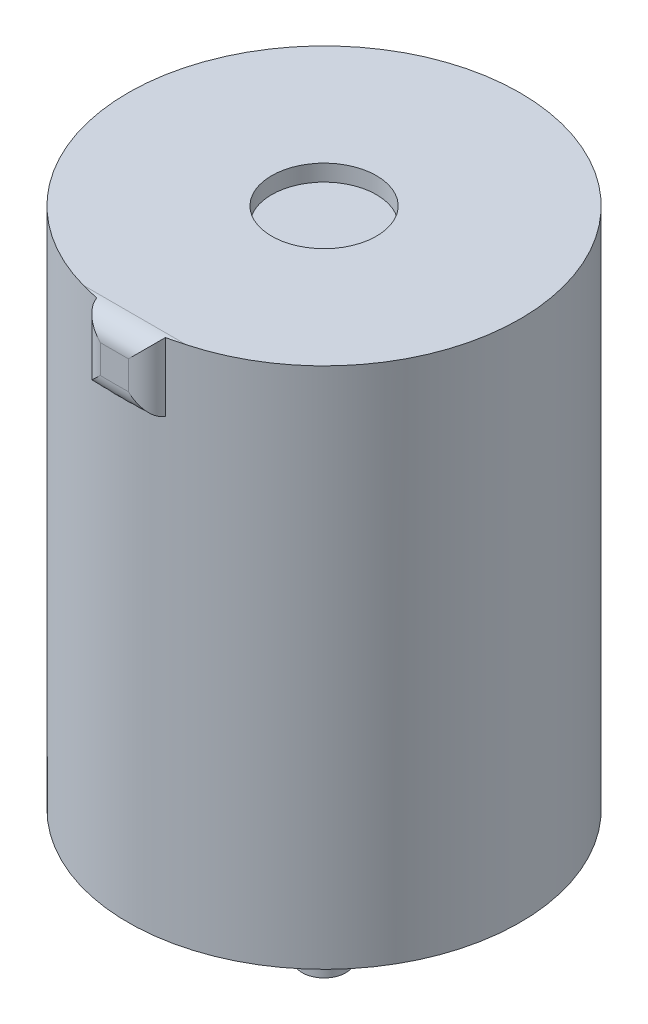
SolidWorks part; units mm, degrees
ref_plane "Front" through (0, 0, 0) normal (0, 0, 1) x (1, 0, 0)
ref_plane "Top" through (0, 0, 0) normal (0, 1, 0) x (1, 0, 0)
ref_plane "Right" through (0, 0, 0) normal (1, 0, 0) x (0, 0, -1)
sketch "Sketch1" plane through (0, 0, 0) normal (0, 0, 1) x (1, 0, 0)
  line L0 (0, -19.05) -> (3.175, -19.05)
  line L1 (3.175, -19.05) -> (3.175, 2.4)
  line L2 (3.175, 2.4) -> (7.645, 2.4)
  line L3 (7.645, 2.4) -> (7.645, 0)
  line L4 (7.645, 0) -> (28.575, 0)
  line L5 (28.575, 0) -> (28.575, 76.2)
  line L6 (28.575, 76.2) -> (7.645, 76.2)
  line L7 (7.645, 76.2) -> (7.645, 73.8)
  line L8 (7.645, 73.8) -> (0, 73.8)
  line L9 (0, 73.8) -> (0, -19.05)
  line L10 (0, 0) -> (0, 63.4299) construction
  dimension "D1" = 6.35
  dimension "D2" = 57.15
  dimension "D3" = 19.05
  dimension "D4" = 76.2
  dimension "D5" = 2.4
  dimension "D6" = 15.29
revolve "Revolve1" add sketch "Sketch1" angle 360 about L10
hole_wizard "#6-32 Tapped Hole1" positions "Sketch2" profile "Sketch4" tap size "#6-32" standard "ANSI Inch"
sketch "Sketch2" plane through (0, 0, 0) normal (0, -1, 0) x (-1, 0, 0)
  line L0 (0, 0) -> (0, 19.05) construction
  line L3 (0, 0) -> (4.9305, 18.4009) construction
  circle A0 centre (0, 0) radius 19.05
  point P0 (4.9305, 18.4009)
  dimension "D1" = 38.1
  dimension "D2" = 15
sketch "Sketch4" plane through (-4.9305, 0, -18.4009) normal (1, 0, 0) x (0, 0, -1)
  line L0 (0, 0) -> (0, 8.4327)
  line L1 (0, 8.4327) -> (1.3525, 7.62)
  line L2 (1.3525, 7.62) -> (1.3525, 0)
  line L5 (1.3525, 0) -> (0, 0)
  line L10 (0, 8.4327) -> (-1.3526, 7.62) construction
  line L11 (0, -6.35) -> (0, 107.95) construction
  dimension "Tap Drill Dia." = 2.7051
  dimension "Tap Drill Depth" = 7.62
  dimension "Drill Angle" = 118
cosmetic thread "Hole Thread1" parameters "D1"=7.01, "D2"=3.5052
pattern_circular "CirPattern1" count 4 over 360 about axis through (0, 0, 0) along (0, 1, 0) of "#6-32 Tapped Hole1"
ref_plane "Plane1" through (0, 0, 28.575) normal (0, 0, 1) x (1, 0, 0)
sketch "Sketch5" plane through (0, 0, 28.575) normal (0, 0, 1) x (1, 0, 0)
  line L0 (28.575, 76.2) -> (-28.575, 76.2) construction
  line L1 (-5, 76.2) -> (5, 76.2)
  line L2 (-5, 76.2) -> (-5, 66.2)
  line L3 (-5, 66.2) -> (5, 66.2)
  line L4 (5, 76.2) -> (5, 66.2)
  point P4 (0, 76.2)
  dimension "D1" = 10
  dimension "D2" = 10
extrude "Boss-Extrude1" add sketch "Sketch5" along normal blind 2 and the other way up to next
fillet "Fillet1" radius 3 4 edges at (0, 76.2, 30.575) (-5, 71.2, 30.575) (0, 66.2, 30.575) (5, 71.2, 30.575)
